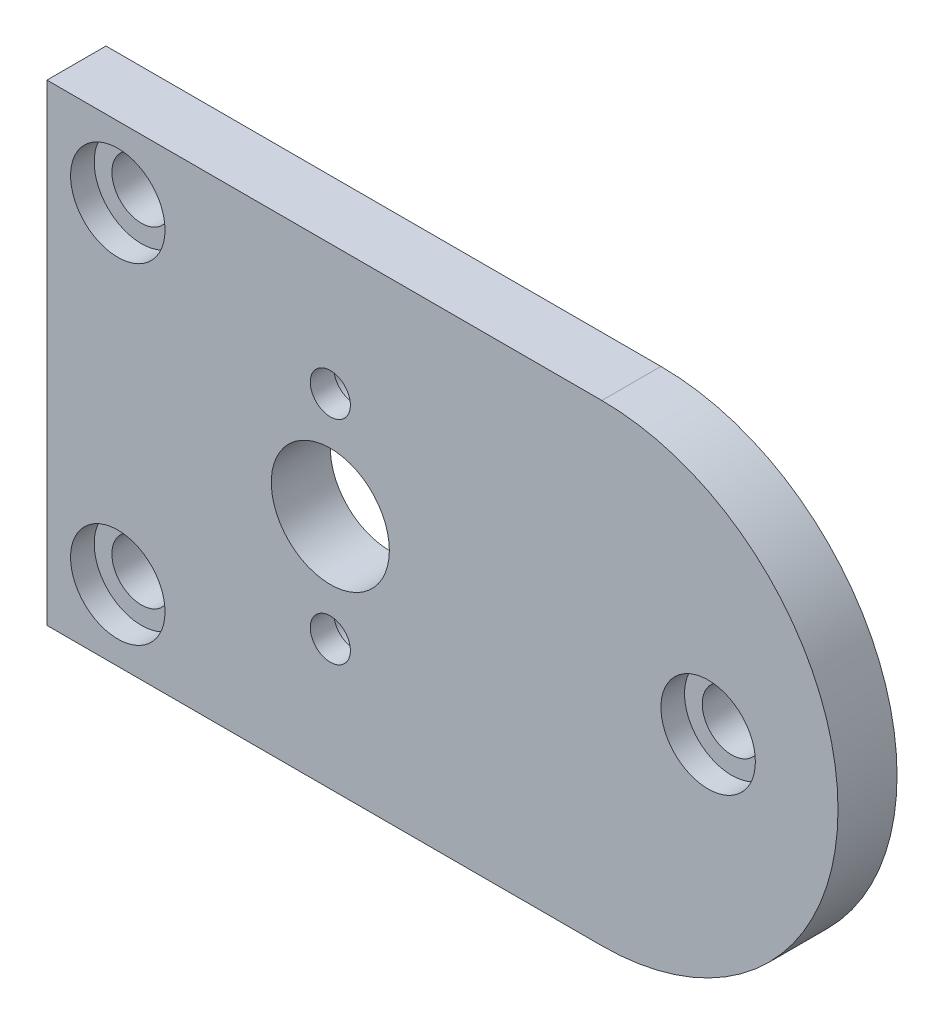
SolidWorks part; units mm, degrees
ref_plane "前视基准面" through (0, 0, 0) normal (0, 0, 1) x (1, 0, 0)
ref_plane "上视基准面" through (0, 0, 0) normal (0, 1, 0) x (1, 0, 0)
ref_plane "右视基准面" through (0, 0, 0) normal (1, 0, 0) x (0, 0, -1)
other "Configuration Table"
sketch "草图1" plane through (0, 0, 0) normal (0, 0, 1) x (1, 0, 0)
  line L0 (0, 4.5) -> (0, -4.5) construction
  line L1 (-11.5, -10) -> (11.5, -10)
  line L2 (-11.5, -10) -> (-11.5, 10)
  line L3 (-11.5, 10) -> (11.5, 10)
  line L4 (11.5, -10) -> (11.5, 10)
  line L5 (-11.5, -10) -> (11.5, 10) construction
  line L6 (-11.5, 10) -> (11.5, -10) construction
  line L8 (-11.5, 10) -> (-12, 10)
  line L9 (-11.5, 10) -> (-11.5, -10)
  line L10 (-11.5, -10) -> (-12, -10)
  line L11 (-12, 10) -> (-12, -10)
  circle A4 centre (0, 4.5) radius 0.85
  circle A5 centre (0, -4.5) radius 0.85
  circle A6 centre (0, 4.5) radius 1.1
  circle A7 centre (0, -4.5) radius 1.1
  circle A8 centre (0, 0) radius 2.5
  circle A9 centre (-9, 7) radius 1.25
  circle A10 centre (-9, 7) radius 2
  circle A11 centre (-9, -7) radius 1.25
  circle A12 centre (-9, -7) radius 2
  circle A14 centre (11.5, 0) radius 10
  circle A15 centre (16, 0) radius 1.25
  circle A16 centre (16, 0) radius 2
  point P0 (0, 0)
  dimension "D1" = 1.7
  dimension "D2" = 1.7
  dimension "D3" = 2.2
  dimension "D5" = 5
  dimension "D8" = 2.5
  dimension "D9" = 4
  dimension "D4" = 9
  dimension "D6" = 11.5
  dimension "D7" = 20
  dimension "D10" = 3
  dimension "D11" = 3
  dimension "D12" = 0.5
  dimension "D13" = 3
  dimension "D14" = 16
extrude "凸台-拉伸1" add sketch "草图1" along normal mid plane 2.5 contours L8 L11 L10 L2 | L4 A14 | A16 A15 | L2 L3 L4 L1 | A4 | A5 | A8 | A9 | A11 region at (-11.75, 0, 0) region at (11.7236, 0, 0) region at (14.0566, 0, 0)
extrude "切除-拉伸1" cut sketch "草图1<4>" against normal offset from surface (1.5 mm away) 1 from surface contours A6 | A7 up to face at (2.25, 0, -1.25) starting at face at (2.25, 0, 1.25)
sketch "草图1<4>" plane through (0, 0, 0) normal (0, 0, 1) x (1, 0, 0) same geometry as "草图1"
extrude "切除-拉伸3" cut sketch "草图1<5>" along normal offset from surface (1 mm away) 1.5 from surface contours A16 | A12 | A10 up to face at (1.1, 4.5, 1.25) starting at face at (2.25, 0, -1.25)
sketch "草图1<5>" plane through (0, 0, 0) normal (0, 0, 1) x (1, 0, 0) same geometry as "草图1"
ref_plane "基准面1" through (0, 0, 11.25) normal (0, 0, 1) x (1, 0, 0)
mirror "镜向1" about plane through (0, 0, 11.25) normal (0, 0, 1) of bodies 152
sketch "草图2" plane through (0, 0, 11.25) normal (0, 0, 1) x (1, 0, 0)
  line L1 (-19.5089, 12.5886) -> (24.1877, 12.5886)
  line L2 (-19.5089, 12.5886) -> (-19.5089, -14.6931)
  line L3 (-19.5089, -14.6931) -> (24.1877, -14.6931)
  line L4 (24.1877, 12.5886) -> (24.1877, -14.6931)
extrude "切除-拉伸4" cut sketch "草图2" against normal through all
